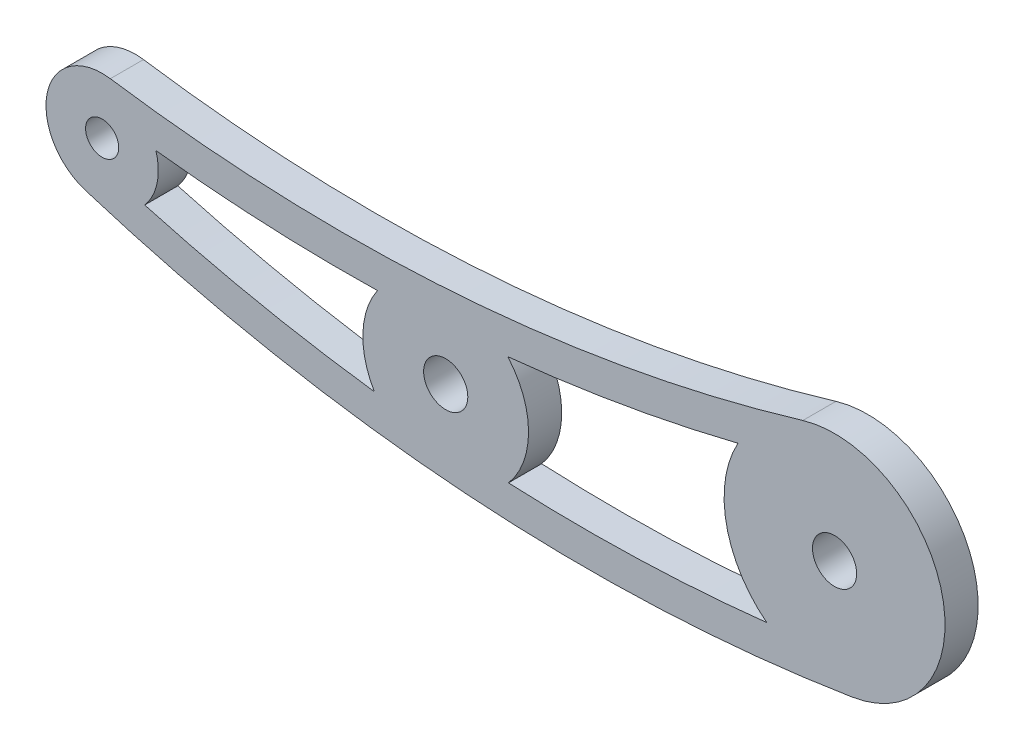
SolidWorks part; units mm, degrees
material "Plain Carbon Steel"
ref_plane "Front Plane" through (0, 0, 0) normal (0, 0, 1) x (1, 0, 0)
ref_plane "Top Plane" through (0, 0, 0) normal (0, 1, 0) x (1, 0, 0)
ref_plane "Right Plane" through (0, 0, 0) normal (1, 0, 0) x (0, 0, -1)
sketch "Sketch1" plane through (0, 0, 0) normal (0, 0, 1) x (1, 0, 0)
  line L0 (0, 0) -> (66.3, 0)
  line L1 (0, -8) -> (66.3, -8)
  line L2 (0, 8) -> (66.3, 8)
  line L3 (0, -5) -> (66.3, -5)
  circle A0 centre (66.3, 0) radius 2
  circle A1 centre (0, 0) radius 1.5
  arc A2 (0, -8) -> (0, 8) centre (0, 0) cw
  arc A3 (66.3, -8) -> (66.3, 8) centre (66.3, 0) ccw
  circle A4 centre (31.1, -3.74) radius 1.5
  circle A5 centre (33.15, 176.6537) radius 184.6537
  circle A6 centre (33.15, 176.6537) radius 174.6537
  circle A7 centre (0, 0) radius 5.0835
  circle A8 centre (66.3, 0) radius 5.0835
  dimension "D2" = 4
  dimension "D1" = 3
extrude "Extrude1" add sketch "Sketch1" along normal blind 3 contours A7 A5 L3 A1 | A8 L0 A7 L3 A4 | A8 A6 A7 L0 | A8 L3 A5 A0 | A8 L3 A4 A7 A5 | A5 A7 L3 | L3 A8 A5 region at (3.7955, -3.1624, 0) region at (33.15, 1.5509, 0) region at (33.1991, -2.5214, 0) region at (62.4982, 3.1548, 0) region at (0.4491, -5.0241, 0) region at (33.1541, -6.2037, 0) region at (65.8509, -5.0241, 0)
sketch "Sketch2" plane through (0, 0, 3) normal (0, 0, 1) x (1, 0, 0)
  circle A0 centre (31.1, -3.74) radius 7.5 construction
  arc A1 (67.8926, -9.8724) -> (63.4272, 9.5785) centre (66.3, 0) ccw
  arc A2 (0.742, 5.029) -> (63.4272, 9.5785) centre (21.8615, 148.164) ccw
  arc A3 (0.9376, 4.9963) -> (-2.1931, -4.5861) centre (0, 0) ccw construction
  arc A4 (67.8926, -9.8724) -> (-1.5236, -4.8498) centre (43.8061, 139.438) cw
  arc A6 (0.742, 5.029) -> (-1.5236, -4.8498) centre (0, 0) ccw
  arc M1 (-2.1931, -4.5861) -> (68.4931, -4.5861) centre (33.15, 176.6537) ccw
  arc M2 (68.4931, -4.5861) -> (65.3624, 4.9963) centre (66.3, 0) ccw
  arc M3 (65.3624, 4.9963) -> (0.9376, 4.9963) centre (33.15, 176.6537) cw
  arc M4 (0.9376, 4.9963) -> (-2.1931, -4.5861) centre (0, 0) ccw
  circle M5 centre (31.1, -3.74) radius 1.5
  circle M6 centre (0, 0) radius 1.5
  circle M7 centre (66.3, 0) radius 2
  dimension "D1" = 15
  dimension "D2" = 20
extrude "Boss-Extrude1" add sketch "Sketch2" against normal blind 3 contours M4 M1 M2 M3 M5 M7 M6 | A6 A4 A1 A2 M1 M4 M3 M2 region at (32.9504, -10.5958, 3) region at (32.9172, -1.7824, 3)
sketch "Sketch3" plane through (0, 0, 3) normal (0, 0, 1) x (1, 0, 0)
  circle A0 centre (66.3, 0) radius 2
  circle A1 centre (31.1, -3.74) radius 2
  arc A4 (3.8522, -3.317) -> (4.8693, 1.4601) centre (0, 0) ccw
  arc A5 (24.9211, 0.511) -> (24.6452, -7.5591) centre (31.1, -3.74) ccw
  arc A6 (57.5597, 4.8587) -> (60.1654, -7.8972) centre (66.3, 0) ccw
  arc A7 (36.7182, 1.2285) -> (57.5597, 4.8587) centre (21.8615, 148.164) ccw
  arc A8 (0.3041, 2.0612) -> (-0.6245, -1.9877) centre (0, 0) ccw
  arc A9 (-0.6245, -1.9877) -> (67.4148, -6.9107) centre (43.8061, 139.438) ccw
  arc A10 (67.4148, -6.9107) -> (64.289, 6.7049) centre (66.3, 0) ccw
  arc A11 (0.3041, 2.0612) -> (64.289, 6.7049) centre (21.8615, 148.164) ccw
  arc A13 (3.8522, -3.317) -> (24.6452, -7.5591) centre (43.8061, 139.438) ccw
  arc A15 (4.8693, 1.4601) -> (24.9211, 0.511) centre (21.8615, 148.164) ccw
  arc A16 (36.7813, -8.6361) -> (60.1654, -7.8972) centre (43.8061, 139.438) ccw
  arc A17 (36.7813, -8.6361) -> (36.7182, 1.2285) centre (31.1, -3.74) ccw
  dimension "D2" = 4
  dimension "D3" = 4
  dimension "D1" = 3
extrude "Cut-Extrude1" cut sketch "Sketch3" against normal blind 5
move or copy body "Body-Move/Copy1" [suppressed] bodies to move or copy 105
move or copy body "Body-Move/Copy2" [suppressed] bodies to move or copy 105
move or copy body "Body-Move/Copy3" [suppressed] bodies to move or copy 105
